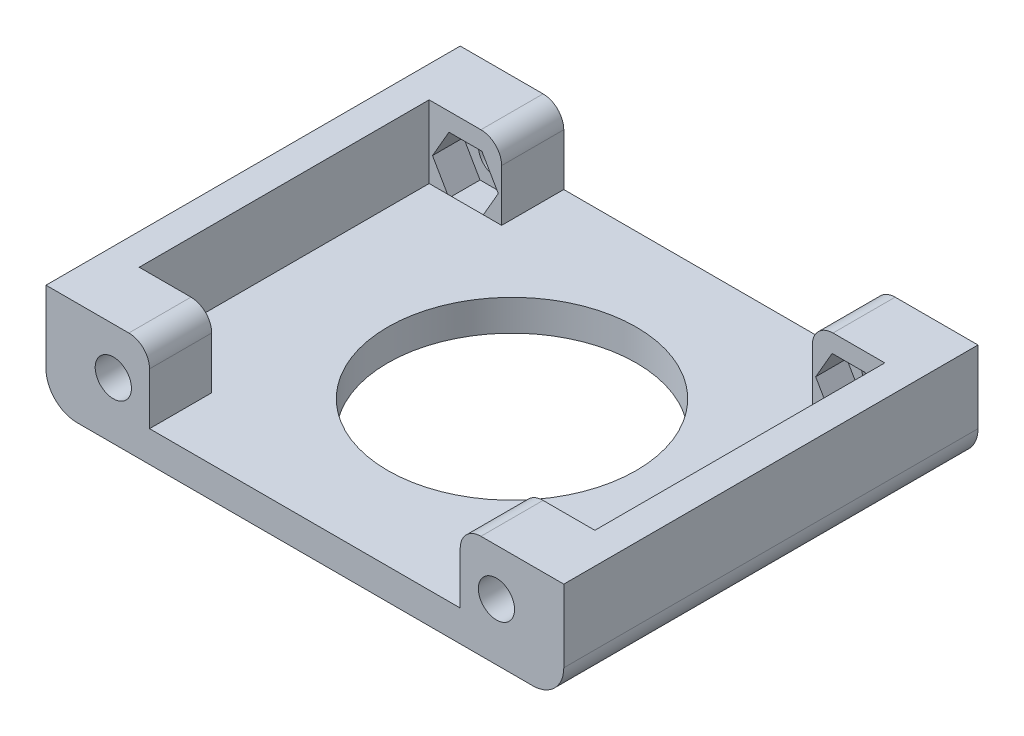
SolidWorks part; units mm, degrees
ref_plane "Front Plane" through (0, 0, 0) normal (0, 0, 1) x (1, 0, 0)
ref_plane "Top Plane" through (0, 0, 0) normal (0, 1, 0) x (1, 0, 0)
ref_plane "Right Plane" through (0, 0, 0) normal (1, 0, 0) x (0, 0, -1)
sketch "Sketch1" plane through (0, 0, 0) normal (0, 1, 0) x (1, 0, 0)
  line L1 (-25, 20) -> (25, 20)
  line L2 (-25, 20) -> (-25, -20)
  line L3 (-25, -20) -> (25, -20)
  line L4 (25, 20) -> (25, -20)
  line L5 (-25, 20) -> (25, -20) construction
  line L6 (-25, -20) -> (25, 20) construction
  point P0 (0, 0)
  dimension "D1" = 50
  dimension "D2" = 40
extrude "Boss-Extrude1" add sketch "Sketch1" along normal blind 3
sketch "Sketch2" plane through (0, 3, 0) normal (0, 1, 0) x (1, 0, 0)
  circle A0 centre (0, 0) radius 12
  dimension "D1" = 24
extrude "Cut-Extrude1" cut sketch "Sketch2" against normal through all
sketch "Sketch3" plane through (0, 3, 0) normal (0, 1, 0) x (1, 0, 0)
  line L0 (-25, -20) -> (25, -20) construction
  line L1 (-25, 20) -> (-22, 20)
  line L2 (-25, 20) -> (-25, -20)
  line L3 (-25, -20) -> (-22, -20)
  line L4 (-22, 20) -> (-22, -20)
  line L6 (22, -20) -> (25, -20)
  line L7 (22, -20) -> (22, 20)
  line L8 (22, 20) -> (25, 20)
  line L9 (25, -20) -> (25, 20)
  dimension "D1" = 3
extrude "Boss-Extrude2" add sketch "Sketch3" along normal blind 7
sketch "Sketch4" plane through (0, 0, 20) normal (0, 0, 1) x (1, 0, 0)
  line L1 (-22, 3) -> (-15, 3)
  line L2 (-22, 3) -> (-22, 10)
  line L3 (-22, 10) -> (-15, 10)
  line L4 (-15, 3) -> (-15, 10)
  line L5 (22, 3) -> (15, 3)
  line L6 (22, 3) -> (22, 10)
  line L7 (22, 10) -> (15, 10)
  line L8 (15, 3) -> (15, 10)
  dimension "D2" = 7
  dimension "6" = 7
extrude "Boss-Extrude3" add sketch "Sketch4" against normal blind 6
sketch "Sketch5" plane through (0, 0, 20) normal (0, 0, 1) x (1, 0, 0)
  line L0 (-18.5, 10) -> (-18.5, 5.5) construction
  line L2 (18.5, 10) -> (18.5, 5.5) construction
  line L3 (-25, 0) -> (25, 0) construction
  line L4 (-18.5, 5.5) -> (18.5, 5.5) construction
  line L6 (-22, 10) -> (-15, 10) construction
  line L7 (-25, 10) -> (-15, 10) construction
  line L8 (15, 10) -> (22, 10) construction
  line L9 (15, 10) -> (15, 3) construction
  line L10 (15, 10) -> (25, 10) construction
  circle A0 centre (-18.5, 5.5) radius 1.75
  circle A1 centre (18.5, 5.5) radius 1.75
  dimension "D1" = 3.5
  dimension "D2" = 3.5
  dimension "D3" = 5.5
extrude "Cut-Extrude2" cut sketch "Sketch5" against normal through all
mirror "Mirror1" about plane through (0, 0, 0) normal (0, 0, 1) of "Cut-Extrude2", "Boss-Extrude3"
sketch "Sketch6" plane through (0, 0, -14) normal (0, 0, 1) x (1, 0, 0)
  line L7 (-15.3246, 5.5) -> (-16.9123, 8.25)
  line L8 (-16.9123, 8.25) -> (-20.0877, 8.25)
  line L9 (-20.0877, 8.25) -> (-21.6754, 5.5)
  line L10 (-21.6754, 5.5) -> (-20.0877, 2.75)
  line L11 (-20.0877, 2.75) -> (-16.9123, 2.75)
  line L12 (-16.9123, 2.75) -> (-15.3246, 5.5)
  circle A0 centre (-18.5, 5.5) radius 2.75 construction
  dimension "D1" = 5.5
extrude "Cut-Extrude3" cut sketch "Sketch6" against normal blind 3
mirror "Mirror2" about plane through (0, 0, 0) normal (1, 0, 0) of "Cut-Extrude3"
mirror "Mirror3" about plane through (0, 0, 0) normal (0, 0, 1) of "Mirror2"
fillet "Fillet1" radius 3 2 edges at (-25, 0, 0) (25, 0, 0)
fillet "Fillet2" radius 2 4 edges at (15, 10, 17) (15, 10, -17) (-15, 10, -17) (-15, 10, 17)
